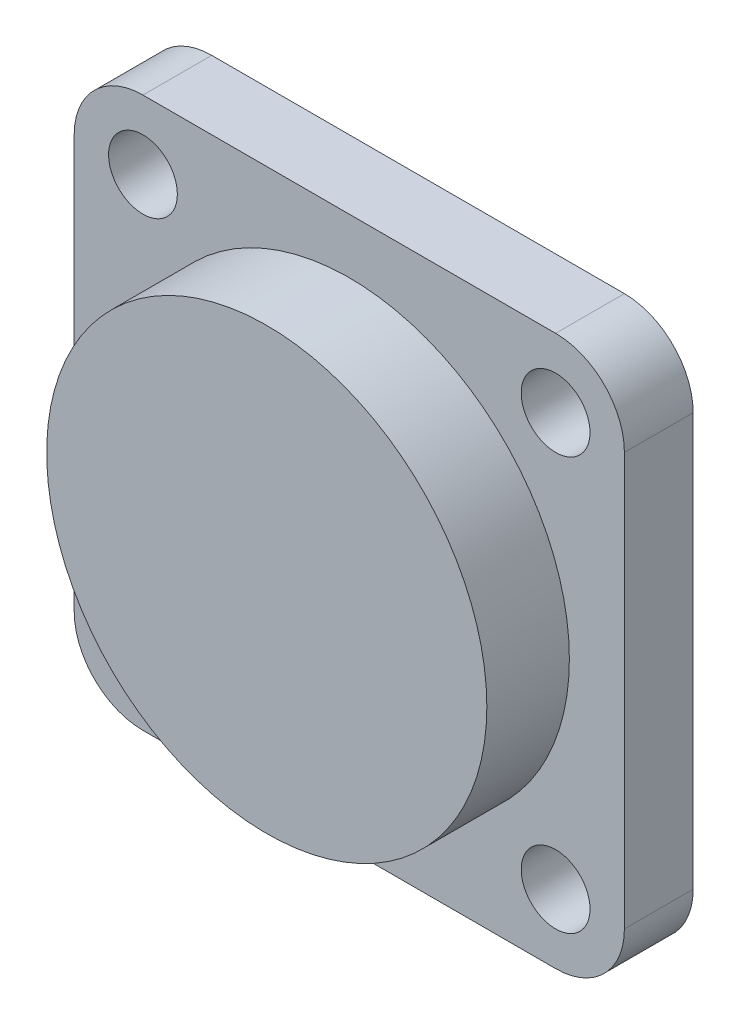
SolidWorks part; units mm, degrees
ref_plane "Front Plane" through (0, 0, 0) normal (0, 0, 1) x (1, 0, 0)
ref_plane "Top Plane" through (0, 0, 0) normal (0, 1, 0) x (1, 0, 0)
ref_plane "Right Plane" through (0, 0, 0) normal (1, 0, 0) x (0, 0, -1)
sketch "Sketch1" plane through (0, 0, 0) normal (0, 0, 1) x (1, 0, 0)
  line L1 (-20, 20) -> (20, 20)
  line L2 (-20, 20) -> (-20, -20)
  line L3 (-20, -20) -> (20, -20)
  line L4 (20, 20) -> (20, -20)
  line L5 (-20, 20) -> (20, -20) construction
  line L6 (-20, -20) -> (20, 20) construction
  line L7 (-15, 15) -> (15, 15) construction
  line L8 (-15, 15) -> (-15, -15) construction
  line L9 (-15, -15) -> (15, -15) construction
  line L10 (15, 15) -> (15, -15) construction
  line L11 (-15, 15) -> (15, -15) construction
  line L12 (-15, -15) -> (15, 15) construction
  circle A0 centre (-15, 15) radius 2.5
  circle A1 centre (15, 15) radius 2.5
  circle A2 centre (15, -15) radius 2.5
  circle A3 centre (-15, -15) radius 2.5
  point P0 (0, 0)
  point P6 (0, 0)
  dimension "D4" = 5
  dimension "D1" = 5
  dimension "D2" = 40
  dimension "D3" = 40
extrude "Boss-Extrude1" add sketch "Sketch1" along normal blind 5
sketch "Sketch2" plane through (0, 0, 5) normal (0, 0, 1) x (1, 0, 0)
  circle A0 centre (0, 0) radius 16
  dimension "D1" = 32
extrude "Boss-Extrude2" add sketch "Sketch2" along normal blind 6
fillet "Fillet2" radius 5 4 edges at (-20, -20, 2.5) (20, -20, 2.5) (20, 20, 2.5) (-20, 20, 2.5)
